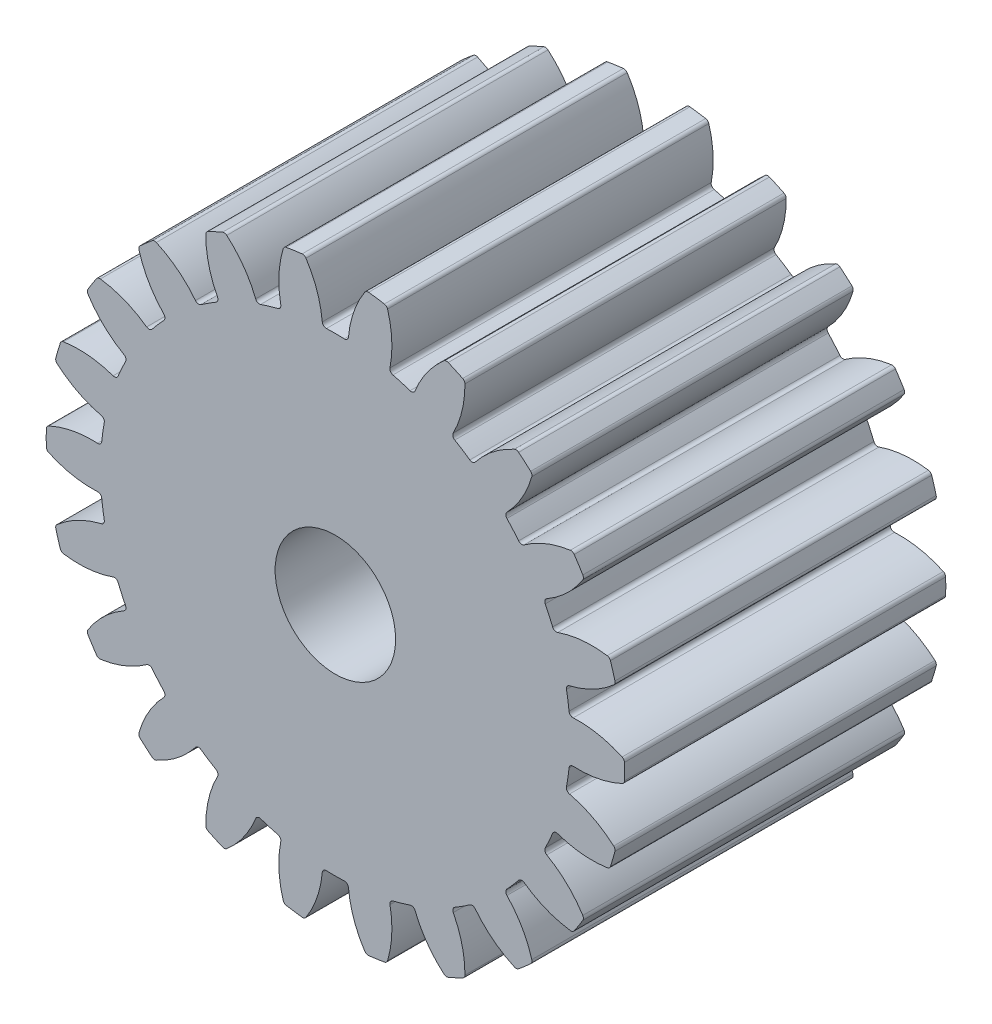
SolidWorks part; units mm, degrees
material "Нержавеющая сталь (ферритная)"
ref_plane "Спереди" through (0, 0, 0) normal (0, 0, 1) x (1, 0, 0)
ref_plane "Сверху" through (0, 0, 0) normal (0, 1, 0) x (1, 0, 0)
ref_plane "Справа" through (0, 0, 0) normal (1, 0, 0) x (0, 0, -1)
sketch "Эскиз1" plane through (0, 0, 0) normal (0, 0, 1) x (1, 0, 0)
  circle A0 centre (0, 0) radius 7.2
  circle A1 centre (0, 0) radius 1.5
  dimension "D1" = 14.4
  dimension "D2" = 3
extrude "Бобышка-Вытянуть1" add sketch "Эскиз1" along normal mid plane 8
sketch "Эскиз2" plane through (0, 0, 0) normal (0, 0, 1) x (1, 0, 0)
  line L0 (0, 0) -> (0, 7.2) construction
  line L1 (-0.319, 5.8413) -> (0, 0) construction
  line L2 (-0.4708, 6.5832) -> (0, 5.2896) construction
  line L3 (-0.4708, 6.5832) -> (0.4708, 6.5832) construction
  line L4 (0.4708, 6.5832) -> (1.4029, 6.4492) construction
  line L5 (0, 0) -> (0.9369, 6.5162) construction
  arc A0 (1.4029, 6.4492) -> (-0.4708, 6.5832) centre (0, 0) ccw construction
  arc A1 (0.319, 5.8413) -> (-0.319, 5.8413) centre (0, 0) ccw
  circle A2 centre (0, 0) radius 7.2 construction
  arc A3 (0.7669, 7.159) -> (-0.7669, 7.159) centre (0, 0) ccw
  arc A4 (0.319, 5.8413) -> (0.7669, 7.159) centre (2.8959, 5.7006) cw
  arc A5 (-0.319, 5.8413) -> (-0.7669, 7.159) centre (-2.8959, 5.7006) ccw
  dimension "D1" = 11.7
  dimension "D2" = 13.2
  dimension "D3" = 20
  dimension "D4" = 8.182
extrude "Вырез-Вытянуть1" cut sketch "Эскиз2" against normal through all both and the other way through all
fillet "Скругление1" radius 0.1 4 edges at (0.7669, 7.159, 0) (0.319, 5.8413, 0) (-0.319, 5.8413, 0) (-0.7669, 7.159, 0)
pattern_circular "Круговой массив1" count 22 over 360 about axis through (0, 0, 4) along (0, 0, -1) of "Вырез-Вытянуть1", "Скругление1"
equation "\"Число зубьев\" = 22"
equation "\"Модуль\"= 0.6мм"
equation "\"D1@Эскиз1\"=\"Число зубьев\"*\"Модуль\"+2*\"Модуль\""
equation "\"D2@Эскиз2\"=\"Число зубьев\"*\"Модуль\""
equation "\"D4@Эскиз2\"= 180 / \"Число зубьев\""
equation "\"D1@Круговой массив1\"=\"Число зубьев\""
equation "\"D1@Эскиз2\"=\"Модуль\" * \"Число зубьев\" - 2.5 * \"Модуль\""
